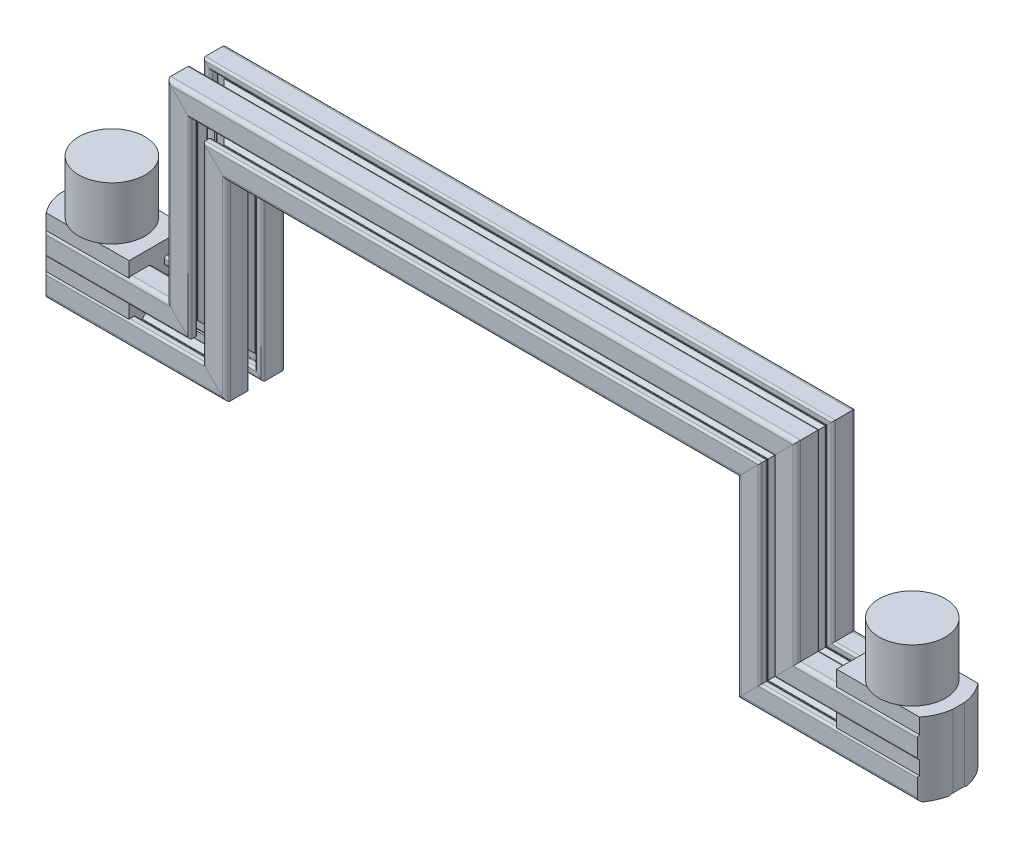
SolidWorks part; units mm, degrees
material "Commercially Pure CP-Ti UNS R50400 (SS)"
ref_plane "Front Plane" through (0, 0, 0) normal (0, 0, 1) x (1, 0, 0)
ref_plane "Top Plane" through (0, 0, 0) normal (0, 1, 0) x (1, 0, 0)
ref_plane "Right Plane" through (0, 0, 0) normal (1, 0, 0) x (0, 0, -1)
sketch "Sketch7" plane through (0, 0, 0) normal (1, 0, 0) x (0, 0, -1)
  line L0 (13.9698, 21.2743) -> (13.5298, 21.2743)
  line L1 (12.0298, 22.7743) -> (12.0298, 23.2743)
  line L2 (13.5298, 24.7743) -> (23.1398, 24.7743)
  line L3 (25.4198, 22.4943) -> (25.4198, 12.8843)
  line L4 (23.9198, 11.3843) -> (23.4198, 11.3843)
  line L5 (21.9198, 12.8843) -> (21.9198, 13.3243)
  line L6 (20.9198, 14.3243) -> (15.3498, 14.3243)
  line L7 (14.9698, 14.7043) -> (14.9698, 20.2743)
  line L8 (21.9589, -6.6897) -> (21.9589, -6.2497)
  line L9 (23.4589, -4.7497) -> (23.9589, -4.7497)
  line L10 (25.4589, -6.2497) -> (25.4589, -15.8597)
  line L11 (23.1789, -18.1397) -> (13.5689, -18.1397)
  line L12 (12.0689, -16.6397) -> (12.0689, -16.1397)
  line L13 (13.5689, -14.6397) -> (14.0089, -14.6397)
  line L14 (15.0089, -13.6397) -> (15.0089, -8.0697)
  line L15 (15.3889, -7.6897) -> (20.9589, -7.6897)
  line L16 (-6.0052, -14.6787) -> (-5.5652, -14.6787)
  line L17 (-4.0652, -16.1787) -> (-4.0652, -16.6787)
  line L18 (-5.5652, -18.1787) -> (-15.1752, -18.1787)
  line L19 (-17.4552, -15.8987) -> (-17.4552, -6.2887)
  line L20 (-15.9552, -4.7887) -> (-15.4552, -4.7887)
  line L21 (-13.9552, -6.2887) -> (-13.9552, -6.7287)
  line L22 (-12.9552, -7.7287) -> (-7.3852, -7.7287)
  line L23 (-7.0052, -8.1087) -> (-7.0052, -13.6787)
  line L24 (1.8289, -2.4886) -> (1.4132, -2.3164)
  line L25 (-1.632, 0.7289) -> (-1.8042, 1.1447)
  line L26 (-1.804, 5.4512) -> (-1.6318, 5.867)
  line L27 (1.4134, 8.9121) -> (1.8292, 9.0843)
  line L28 (6.1358, 9.0842) -> (6.5515, 8.912)
  line L29 (9.5966, 5.8667) -> (9.7688, 5.451)
  line L30 (9.7687, 1.1444) -> (9.5965, 0.7287)
  line L31 (6.5512, -2.3165) -> (6.1355, -2.4887)
  line L32 (-13.9942, 13.2853) -> (-13.9942, 12.8453)
  line L33 (-15.4942, 11.3453) -> (-15.9942, 11.3453)
  line L34 (-17.4942, 12.8453) -> (-17.4942, 22.4553)
  line L35 (-15.2142, 24.7353) -> (-5.6042, 24.7353)
  line L36 (-4.1042, 23.2353) -> (-4.1042, 22.7353)
  line L37 (-5.6042, 21.2353) -> (-6.0442, 21.2353)
  line L38 (-7.0442, 20.2353) -> (-7.0442, 14.6653)
  line L39 (-7.4242, 14.2853) -> (-12.9942, 14.2853)
  line L40 (4.9058, 11.2153) -> (4.0058, 10.7002)
  line L41 (4.0058, 10.7002) -> (3.1058, 11.2153)
  line L42 (3.1058, 11.2153) -> (-2.1975, 11.2153)
  line L43 (-2.4662, 11.3266) -> (-5.9329, 14.7933)
  line L44 (-6.0442, 15.062) -> (-6.0442, 19.3553)
  line L45 (-5.6642, 19.7353) -> (-2.5792, 19.7353)
  line L46 (-1.0592, 21.2553) -> (-1.0592, 24.2153)
  line L47 (-2.5792, 25.7353) -> (-15.4942, 25.7353)
  line L48 (-18.4942, 22.7353) -> (-18.4942, 9.8203)
  line L49 (-16.9742, 8.3003) -> (-14.0142, 8.3003)
  line L50 (-12.4942, 9.8203) -> (-12.4942, 12.9053)
  line L51 (-12.1142, 13.2853) -> (-7.8138, 13.2853)
  line L52 (-7.5451, 13.174) -> (-4.0855, 9.7144)
  line L53 (-3.9742, 9.4457) -> (-3.9742, 4.1353)
  line L54 (-3.9742, 4.1353) -> (-3.4546, 3.2353)
  line L55 (-3.4546, 3.2353) -> (-3.9742, 2.3353)
  line L56 (-3.9742, 2.3353) -> (-3.9742, -2.968)
  line L57 (-4.0855, -3.2367) -> (-7.5522, -6.7034)
  line L58 (-7.8209, -6.8147) -> (-12.1142, -6.8147)
  line L59 (-12.4942, -6.4347) -> (-12.4942, -3.3497)
  line L60 (-14.0142, -1.8297) -> (-16.9742, -1.8297)
  line L61 (-18.4942, -3.3497) -> (-18.4942, -16.2647)
  line L62 (-15.4942, -19.2647) -> (-2.5792, -19.2647)
  line L63 (-1.0592, -17.7447) -> (-1.0592, -14.7847)
  line L64 (-2.5792, -13.2647) -> (-5.6642, -13.2647)
  line L65 (-6.0442, -12.8847) -> (-6.0442, -8.5843)
  line L66 (-5.9329, -8.3156) -> (-2.4733, -4.856)
  line L67 (-2.2046, -4.7447) -> (3.1058, -4.7447)
  line L68 (3.1058, -4.7447) -> (4.0058, -4.2295)
  line L69 (4.0058, -4.2295) -> (4.9058, -4.7447)
  line L70 (4.9058, -4.7447) -> (10.2091, -4.7447)
  line L71 (10.4778, -4.856) -> (13.9445, -8.3227)
  line L72 (14.0558, -8.5914) -> (14.0558, -12.8847)
  line L73 (13.6758, -13.2647) -> (10.5908, -13.2647)
  line L74 (9.0708, -14.7847) -> (9.0708, -17.7447)
  line L75 (10.5908, -19.2647) -> (23.5058, -19.2647)
  line L76 (26.5058, -16.2647) -> (26.5058, -3.3497)
  line L77 (24.9858, -1.8297) -> (22.0258, -1.8297)
  line L78 (20.5058, -3.3497) -> (20.5058, -6.4347)
  line L79 (20.1258, -6.8147) -> (15.8254, -6.8147)
  line L80 (15.5567, -6.7034) -> (12.0971, -3.2438)
  line L81 (11.9858, -2.9751) -> (11.9858, 2.3353)
  line L82 (11.9858, 2.3353) -> (11.4662, 3.2353)
  line L83 (11.4662, 3.2353) -> (11.9858, 4.1353)
  line L84 (11.9858, 4.1353) -> (11.9858, 9.4386)
  line L85 (12.0971, 9.7073) -> (15.5638, 13.174)
  line L86 (15.8325, 13.2853) -> (20.1258, 13.2853)
  line L87 (20.5058, 12.9053) -> (20.5058, 9.8203)
  line L88 (22.0258, 8.3003) -> (24.9858, 8.3003)
  line L89 (26.5058, 9.8203) -> (26.5058, 22.7353)
  line L90 (23.5058, 25.7353) -> (10.5908, 25.7353)
  line L91 (9.0708, 24.2153) -> (9.0708, 21.2553)
  line L92 (10.5908, 19.7353) -> (13.6758, 19.7353)
  line L93 (14.0558, 19.3553) -> (14.0558, 15.0549)
  line L94 (13.9445, 14.7862) -> (10.4849, 11.3266)
  line L95 (10.2162, 11.2153) -> (4.9058, 11.2153)
  arc A0 (14.9698, 20.2743) -> (13.9698, 21.2743) centre (13.9698, 20.2743) ccw
  arc A1 (12.0298, 22.7743) -> (13.5298, 21.2743) centre (13.5298, 22.7743) ccw
  arc A2 (13.5298, 24.7743) -> (12.0298, 23.2743) centre (13.5298, 23.2743) ccw
  arc A3 (25.4198, 22.4943) -> (23.1398, 24.7743) centre (23.1398, 22.4943) ccw
  arc A4 (23.9198, 11.3843) -> (25.4198, 12.8843) centre (23.9198, 12.8843) ccw
  arc A5 (21.9198, 12.8843) -> (23.4198, 11.3843) centre (23.4198, 12.8843) ccw
  arc A6 (21.9198, 13.3243) -> (20.9198, 14.3243) centre (20.9198, 13.3243) ccw
  arc A7 (14.9698, 14.7043) -> (15.3498, 14.3243) centre (15.3498, 14.7043) ccw
  arc A8 (20.9589, -7.6897) -> (21.9589, -6.6897) centre (20.9589, -6.6897) ccw
  arc A9 (23.4589, -4.7497) -> (21.9589, -6.2497) centre (23.4589, -6.2497) ccw
  arc A10 (25.4589, -6.2497) -> (23.9589, -4.7497) centre (23.9589, -6.2497) ccw
  arc A11 (23.1789, -18.1397) -> (25.4589, -15.8597) centre (23.1789, -15.8597) ccw
  arc A12 (12.0689, -16.6397) -> (13.5689, -18.1397) centre (13.5689, -16.6397) ccw
  arc A13 (13.5689, -14.6397) -> (12.0689, -16.1397) centre (13.5689, -16.1397) ccw
  arc A14 (14.0089, -14.6397) -> (15.0089, -13.6397) centre (14.0089, -13.6397) ccw
  arc A15 (15.3889, -7.6897) -> (15.0089, -8.0697) centre (15.3889, -8.0697) ccw
  arc A16 (-7.0052, -13.6787) -> (-6.0052, -14.6787) centre (-6.0052, -13.6787) ccw
  arc A17 (-4.0652, -16.1787) -> (-5.5652, -14.6787) centre (-5.5652, -16.1787) ccw
  arc A18 (-5.5652, -18.1787) -> (-4.0652, -16.6787) centre (-5.5652, -16.6787) ccw
  arc A19 (-17.4552, -15.8987) -> (-15.1752, -18.1787) centre (-15.1752, -15.8987) ccw
  arc A20 (-15.9552, -4.7887) -> (-17.4552, -6.2887) centre (-15.9552, -6.2887) ccw
  arc A21 (-13.9552, -6.2887) -> (-15.4552, -4.7887) centre (-15.4552, -6.2887) ccw
  arc A22 (-13.9552, -6.7287) -> (-12.9552, -7.7287) centre (-12.9552, -6.7287) ccw
  arc A23 (-7.0052, -8.1087) -> (-7.3852, -7.7287) centre (-7.3852, -8.1087) ccw
  arc A24 (1.0363, -0.7421) -> (1.4132, -2.3164) centre (1.7959, -1.3925) ccw
  arc A25 (-0.0577, 0.352) -> (1.0363, -0.7421) centre (3.9823, 3.2978) ccw
  arc A26 (-1.632, 0.7289) -> (-0.0577, 0.352) centre (-0.7081, 1.1116) ccw
  arc A27 (-0.9575, 2.5244) -> (-1.8042, 1.1447) centre (-0.8803, 1.5274) ccw
  arc A28 (-0.9574, 4.0715) -> (-0.9575, 2.5244) centre (3.9823, 3.2978) ccw
  arc A29 (-1.804, 5.4512) -> (-0.9574, 4.0715) centre (-0.8802, 5.0686) ccw
  arc A30 (-0.0575, 6.2439) -> (-1.6318, 5.867) centre (-0.708, 5.4843) ccw
  arc A31 (1.0365, 7.3379) -> (-0.0575, 6.2439) centre (3.9823, 3.2978) ccw
  arc A32 (1.4134, 8.9121) -> (1.0365, 7.3379) centre (1.7961, 7.9882) ccw
  arc A33 (3.2089, 8.2376) -> (1.8292, 9.0843) centre (2.2119, 8.1604) ccw
  arc A34 (4.7561, 8.2376) -> (3.2089, 8.2376) centre (3.9823, 3.2978) ccw
  arc A35 (6.1358, 9.0842) -> (4.7561, 8.2376) centre (5.7531, 8.1603) ccw
  arc A36 (6.9284, 7.3377) -> (6.5515, 8.912) centre (6.1688, 7.9881) ccw
  arc A37 (8.0224, 6.2437) -> (6.9284, 7.3377) centre (3.9823, 3.2978) ccw
  arc A38 (9.5966, 5.8667) -> (8.0224, 6.2437) centre (8.6727, 5.484) ccw
  arc A39 (8.9222, 4.0713) -> (9.7688, 5.451) centre (8.845, 5.0683) ccw
  arc A40 (8.9221, 2.5241) -> (8.9222, 4.0713) centre (3.9823, 3.2978) ccw
  arc A41 (9.7687, 1.1444) -> (8.9221, 2.5241) centre (8.8448, 1.5271) ccw
  arc A42 (8.0222, 0.3518) -> (9.5965, 0.7287) centre (8.6726, 1.1113) ccw
  arc A43 (6.9282, -0.7422) -> (8.0222, 0.3518) centre (3.9823, 3.2978) ccw
  arc A44 (6.5512, -2.3165) -> (6.9282, -0.7422) centre (6.1685, -1.3926) ccw
  arc A45 (4.7558, -1.642) -> (6.1355, -2.4887) centre (5.7528, -1.5648) ccw
  arc A46 (3.2086, -1.642) -> (4.7558, -1.642) centre (3.9823, 3.2978) ccw
  arc A47 (1.8289, -2.4886) -> (3.2086, -1.642) centre (2.2116, -1.5647) ccw
  arc A48 (-12.9942, 14.2853) -> (-13.9942, 13.2853) centre (-12.9942, 13.2853) ccw
  arc A49 (-15.4942, 11.3453) -> (-13.9942, 12.8453) centre (-15.4942, 12.8453) ccw
  arc A50 (-17.4942, 12.8453) -> (-15.9942, 11.3453) centre (-15.9942, 12.8453) ccw
  arc A51 (-15.2142, 24.7353) -> (-17.4942, 22.4553) centre (-15.2142, 22.4553) ccw
  arc A52 (-4.1042, 23.2353) -> (-5.6042, 24.7353) centre (-5.6042, 23.2353) ccw
  arc A53 (-5.6042, 21.2353) -> (-4.1042, 22.7353) centre (-5.6042, 22.7353) ccw
  arc A54 (-6.0442, 21.2353) -> (-7.0442, 20.2353) centre (-6.0442, 20.2353) ccw
  arc A55 (-7.4242, 14.2853) -> (-7.0442, 14.6653) centre (-7.4242, 14.6653) ccw
  arc A56 (-2.4662, 11.3266) -> (-2.1975, 11.2153) centre (-2.1975, 11.5953) ccw
  arc A57 (-6.0442, 15.062) -> (-5.9329, 14.7933) centre (-5.6642, 15.062) ccw
  arc A58 (-5.6642, 19.7353) -> (-6.0442, 19.3553) centre (-5.6642, 19.3553) ccw
  arc A59 (-2.5792, 19.7353) -> (-1.0592, 21.2553) centre (-2.5792, 21.2553) ccw
  arc A60 (-1.0592, 24.2153) -> (-2.5792, 25.7353) centre (-2.5792, 24.2153) ccw
  arc A61 (-15.4942, 25.7353) -> (-18.4942, 22.7353) centre (-15.4942, 22.7353) ccw
  arc A62 (-18.4942, 9.8203) -> (-16.9742, 8.3003) centre (-16.9742, 9.8203) ccw
  arc A63 (-14.0142, 8.3003) -> (-12.4942, 9.8203) centre (-14.0142, 9.8203) ccw
  arc A64 (-12.1142, 13.2853) -> (-12.4942, 12.9053) centre (-12.1142, 12.9053) ccw
  arc A65 (-7.5451, 13.174) -> (-7.8138, 13.2853) centre (-7.8138, 12.9053) ccw
  arc A66 (-3.9742, 9.4457) -> (-4.0855, 9.7144) centre (-4.3542, 9.4457) ccw
  arc A67 (-4.0855, -3.2367) -> (-3.9742, -2.968) centre (-4.3542, -2.968) ccw
  arc A68 (-7.8209, -6.8147) -> (-7.5522, -6.7034) centre (-7.8209, -6.4347) ccw
  arc A69 (-12.4942, -6.4347) -> (-12.1142, -6.8147) centre (-12.1142, -6.4347) ccw
  arc A70 (-12.4942, -3.3497) -> (-14.0142, -1.8297) centre (-14.0142, -3.3497) ccw
  arc A71 (-16.9742, -1.8297) -> (-18.4942, -3.3497) centre (-16.9742, -3.3497) ccw
  arc A72 (-18.4942, -16.2647) -> (-15.4942, -19.2647) centre (-15.4942, -16.2647) ccw
  arc A73 (-2.5792, -19.2647) -> (-1.0592, -17.7447) centre (-2.5792, -17.7447) ccw
  arc A74 (-1.0592, -14.7847) -> (-2.5792, -13.2647) centre (-2.5792, -14.7847) ccw
  arc A75 (-6.0442, -12.8847) -> (-5.6642, -13.2647) centre (-5.6642, -12.8847) ccw
  arc A76 (-5.9329, -8.3156) -> (-6.0442, -8.5843) centre (-5.6642, -8.5843) ccw
  arc A77 (-2.2046, -4.7447) -> (-2.4733, -4.856) centre (-2.2046, -5.1247) ccw
  arc A78 (10.4778, -4.856) -> (10.2091, -4.7447) centre (10.2091, -5.1247) ccw
  arc A79 (14.0558, -8.5914) -> (13.9445, -8.3227) centre (13.6758, -8.5914) ccw
  arc A80 (13.6758, -13.2647) -> (14.0558, -12.8847) centre (13.6758, -12.8847) ccw
  arc A81 (10.5908, -13.2647) -> (9.0708, -14.7847) centre (10.5908, -14.7847) ccw
  arc A82 (9.0708, -17.7447) -> (10.5908, -19.2647) centre (10.5908, -17.7447) ccw
  arc A83 (23.5058, -19.2647) -> (26.5058, -16.2647) centre (23.5058, -16.2647) ccw
  arc A84 (26.5058, -3.3497) -> (24.9858, -1.8297) centre (24.9858, -3.3497) ccw
  arc A85 (22.0258, -1.8297) -> (20.5058, -3.3497) centre (22.0258, -3.3497) ccw
  arc A86 (20.1258, -6.8147) -> (20.5058, -6.4347) centre (20.1258, -6.4347) ccw
  arc A87 (15.5567, -6.7034) -> (15.8254, -6.8147) centre (15.8254, -6.4347) ccw
  arc A88 (11.9858, -2.9751) -> (12.0971, -3.2438) centre (12.3658, -2.9751) ccw
  arc A89 (12.0971, 9.7073) -> (11.9858, 9.4386) centre (12.3658, 9.4386) ccw
  arc A90 (15.8325, 13.2853) -> (15.5638, 13.174) centre (15.8325, 12.9053) ccw
  arc A91 (20.5058, 12.9053) -> (20.1258, 13.2853) centre (20.1258, 12.9053) ccw
  arc A92 (20.5058, 9.8203) -> (22.0258, 8.3003) centre (22.0258, 9.8203) ccw
  arc A93 (24.9858, 8.3003) -> (26.5058, 9.8203) centre (24.9858, 9.8203) ccw
  arc A94 (26.5058, 22.7353) -> (23.5058, 25.7353) centre (23.5058, 22.7353) ccw
  arc A95 (10.5908, 25.7353) -> (9.0708, 24.2153) centre (10.5908, 24.2153) ccw
  arc A96 (9.0708, 21.2553) -> (10.5908, 19.7353) centre (10.5908, 21.2553) ccw
  arc A97 (14.0558, 19.3553) -> (13.6758, 19.7353) centre (13.6758, 19.3553) ccw
  arc A98 (13.9445, 14.7862) -> (14.0558, 15.0549) centre (13.6758, 15.0549) ccw
  arc A99 (10.2162, 11.2153) -> (10.4849, 11.3266) centre (10.2162, 11.5953) ccw
sketch "Sketch1" plane through (0, 0, 0) normal (0, 0, 1) x (1, 0, 0)
  line L0 (0, 0) -> (125, 0)
  line L1 (125, 0) -> (125, 144.6943)
  line L2 (125, 144.6943) -> (337, 144.6943)
  dimension "D1" = 337
  dimension "D2" = 125
sketch "Sketch2" [suppressed] plane through (0, 0, 0) normal (1, 0, 0) x (0, 0, -1)
  line L0 (-33.5, -41) -> (-31.5, -41)
  line L1 (-31.5, -43) -> (-42, -43)
  line L2 (-43, -42) -> (-43, -31.5)
  line L3 (-41, -31.5) -> (-41, -33.5)
  line L4 (-40, -34.5) -> (-34.88, -34.5)
  line L5 (-34.5, -34.88) -> (-34.5, -40)
  line L6 (-16.657, -26.2238) -> (-18.284, -25.188)
  line L7 (-19.8123, -26.7162) -> (-18.7764, -28.3429)
  line L8 (-21.0015, -29.2647) -> (-21.4195, -27.3819)
  line L9 (-23.5808, -27.3818) -> (-23.9986, -29.2645)
  line L10 (-26.2238, -28.343) -> (-25.188, -26.716)
  line L11 (-26.7162, -25.1877) -> (-28.3429, -26.2236)
  line L12 (-29.2647, -23.9985) -> (-27.3819, -23.5805)
  line L13 (-27.3818, -21.4192) -> (-29.2645, -21.0014)
  line L14 (-28.343, -18.7762) -> (-26.716, -19.812)
  line L15 (-25.1877, -18.2838) -> (-26.2236, -16.6571)
  line L16 (-23.9985, -15.7353) -> (-23.5805, -17.6181)
  line L17 (-21.4192, -17.6182) -> (-21.0014, -15.7355)
  line L18 (-18.7762, -16.657) -> (-19.812, -18.284)
  line L19 (-18.2838, -19.8123) -> (-16.6571, -18.7764)
  line L20 (-15.7353, -21.0015) -> (-17.6181, -21.4195)
  line L21 (-17.6182, -23.5808) -> (-15.7355, -23.9986)
  line L22 (41, -33.5) -> (41, -31.5)
  line L23 (43, -31.5) -> (43, -42)
  line L24 (42, -43) -> (31.5, -43)
  line L25 (31.5, -41) -> (33.5, -41)
  line L26 (34.5, -40) -> (34.5, -34.88)
  line L27 (34.88, -34.5) -> (40, -34.5)
  line L28 (26.7162, -19.8123) -> (28.3429, -18.7764)
  line L29 (29.2647, -21.0015) -> (27.3819, -21.4195)
  line L30 (27.3818, -23.5808) -> (29.2645, -23.9986)
  line L31 (28.343, -26.2238) -> (26.716, -25.188)
  line L32 (25.1877, -26.7162) -> (26.2236, -28.3429)
  line L33 (23.9985, -29.2647) -> (23.5805, -27.3819)
  line L34 (21.4192, -27.3818) -> (21.0014, -29.2645)
  line L35 (18.7762, -28.343) -> (19.812, -26.716)
  line L36 (18.2838, -25.1877) -> (16.6571, -26.2236)
  line L37 (15.7353, -23.9985) -> (17.6181, -23.5805)
  line L38 (17.6182, -21.4192) -> (15.7355, -21.0014)
  line L39 (16.657, -18.7762) -> (18.284, -19.812)
  line L40 (19.8123, -18.2838) -> (18.7764, -16.6571)
  line L41 (21.0015, -15.7353) -> (21.4195, -17.6181)
  line L42 (23.5808, -17.6182) -> (23.9986, -15.7355)
  line L43 (26.2238, -16.657) -> (25.188, -18.284)
  line L44 (34.5, 34.88) -> (34.5, 40)
  line L45 (33.5, 41) -> (31.5, 41)
  line L46 (31.5, 43) -> (42, 43)
  line L47 (43, 42) -> (43, 31.5)
  line L48 (41, 31.5) -> (41, 33.5)
  line L49 (40, 34.5) -> (34.88, 34.5)
  line L50 (26.7162, 25.1877) -> (28.3429, 26.2236)
  line L51 (29.2647, 23.9985) -> (27.3819, 23.5805)
  line L52 (27.3818, 21.4192) -> (29.2645, 21.0014)
  line L53 (28.343, 18.7762) -> (26.716, 19.812)
  line L54 (25.1877, 18.2838) -> (26.2236, 16.6571)
  line L55 (23.9985, 15.7353) -> (23.5805, 17.6181)
  line L56 (21.4192, 17.6182) -> (21.0014, 15.7355)
  line L57 (18.7762, 16.657) -> (19.812, 18.284)
  line L58 (18.2838, 19.8123) -> (16.6571, 18.7764)
  line L59 (15.7353, 21.0015) -> (17.6181, 21.4195)
  line L60 (17.6182, 23.5808) -> (15.7355, 23.9986)
  line L61 (16.657, 26.2238) -> (18.284, 25.188)
  line L62 (19.8123, 26.7162) -> (18.7764, 28.3429)
  line L63 (21.0015, 29.2647) -> (21.4195, 27.3819)
  line L64 (23.5808, 27.3818) -> (23.9986, 29.2645)
  line L65 (26.2238, 28.343) -> (25.188, 26.716)
  line L66 (-41, 33.5) -> (-41, 31.5)
  line L67 (-43, 31.5) -> (-43, 42)
  line L68 (-42, 43) -> (-31.5, 43)
  line L69 (-31.5, 41) -> (-33.5, 41)
  line L70 (-34.5, 40) -> (-34.5, 34.88)
  line L71 (-34.88, 34.5) -> (-40, 34.5)
  line L72 (-16.657, 18.7762) -> (-18.284, 19.812)
  line L73 (-19.8123, 18.2838) -> (-18.7764, 16.6571)
  line L74 (-21.0015, 15.7353) -> (-21.4195, 17.6181)
  line L75 (-23.5808, 17.6182) -> (-23.9986, 15.7355)
  line L76 (-26.2238, 16.657) -> (-25.188, 18.284)
  line L77 (-26.7162, 19.8123) -> (-28.3429, 18.7764)
  line L78 (-29.2647, 21.0015) -> (-27.3819, 21.4195)
  line L79 (-27.3818, 23.5808) -> (-29.2645, 23.9986)
  line L80 (-28.343, 26.2238) -> (-26.716, 25.188)
  line L81 (-25.1877, 26.7162) -> (-26.2236, 28.3429)
  line L82 (-23.9985, 29.2647) -> (-23.5805, 27.3819)
  line L83 (-21.4192, 27.3818) -> (-21.0014, 29.2645)
  line L84 (-18.7762, 28.343) -> (-19.812, 26.716)
  line L85 (-18.2838, 25.1877) -> (-16.6571, 26.2236)
  line L86 (-15.7353, 23.9985) -> (-17.6181, 23.5805)
  line L87 (-17.6182, 21.4192) -> (-15.7355, 21.0014)
  line L88 (39, -10.16) -> (33.3774, -10.16)
  line L89 (31.9632, -10.7458) -> (29.8203, -12.8887)
  line L90 (29.5516, -13) -> (23.4, -13)
  line L91 (23.4, -13) -> (22.5, -13.5151)
  line L92 (22.5, -13.5151) -> (21.6, -13)
  line L93 (21.6, -13) -> (15, -13)
  line L94 (13, -15) -> (13, -21.6)
  line L95 (13, -21.6) -> (13.5196, -22.5)
  line L96 (13.5196, -22.5) -> (13, -23.4)
  line L97 (13, -23.4) -> (13, -29.5516)
  line L98 (12.8887, -29.8203) -> (11.3787, -31.3303)
  line L99 (10.5, -33.4516) -> (10.5, -40)
  line L100 (11.5, -41) -> (13.5, -41)
  line L101 (13.5, -43) -> (-13.5, -43)
  line L102 (-13.5, -41) -> (-11.5, -41)
  line L103 (-10.5, -40) -> (-10.5, -33.4516)
  line L104 (-11.3787, -31.3303) -> (-12.8887, -29.8203)
  line L105 (-13, -29.5516) -> (-13, -23.4)
  line L106 (-13, -23.4) -> (-13.5196, -22.5)
  line L107 (-13.5196, -22.5) -> (-13, -21.6)
  line L108 (-13, -21.6) -> (-13, -15)
  line L109 (-15, -13) -> (-21.6, -13)
  line L110 (-21.6, -13) -> (-22.5, -13.5151)
  line L111 (-22.5, -13.5151) -> (-23.4, -13)
  line L112 (-23.4, -13) -> (-29.5516, -13)
  line L113 (-29.8203, -12.8887) -> (-31.9632, -10.7458)
  line L114 (-33.3774, -10.16) -> (-39, -10.16)
  line L115 (-41, -12.16) -> (-41, -13.5)
  line L116 (-43, -13.5) -> (-43, 13.5)
  line L117 (-41, 13.5) -> (-41, 12.16)
  line L118 (-39, 10.16) -> (-33.3774, 10.16)
  line L119 (-31.9632, 10.7458) -> (-29.8203, 12.8887)
  line L120 (-29.5516, 13) -> (-23.4, 13)
  line L121 (-23.4, 13) -> (-22.5, 13.5151)
  line L122 (-22.5, 13.5151) -> (-21.6, 13)
  line L123 (-21.6, 13) -> (-15, 13)
  line L124 (-13, 15) -> (-13, 21.6)
  line L125 (-13, 21.6) -> (-13.5196, 22.5)
  line L126 (-13.5196, 22.5) -> (-13, 23.4)
  line L127 (-13, 23.4) -> (-13, 29.5516)
  line L128 (-12.8887, 29.8203) -> (-11.3787, 31.3303)
  line L129 (-10.5, 33.4516) -> (-10.5, 40)
  line L130 (-11.5, 41) -> (-13.5, 41)
  line L131 (-13.5, 43) -> (13.5, 43)
  line L132 (13.5, 41) -> (11.5, 41)
  line L133 (10.5, 40) -> (10.5, 33.4516)
  line L134 (11.3787, 31.3303) -> (12.8887, 29.8203)
  line L135 (13, 29.5516) -> (13, 23.4)
  line L136 (13, 23.4) -> (13.5196, 22.5)
  line L137 (13.5196, 22.5) -> (13, 21.6)
  line L138 (13, 21.6) -> (13, 15)
  line L139 (15, 13) -> (21.6, 13)
  line L140 (21.6, 13) -> (22.5, 13.5151)
  line L141 (22.5, 13.5151) -> (23.4, 13)
  line L142 (23.4, 13) -> (29.5516, 13)
  line L143 (29.8203, 12.8887) -> (31.9581, 10.7509)
  line L144 (33.3723, 10.1651) -> (39, 10.1651)
  line L145 (41, 12.1651) -> (41, 13.5)
  line L146 (43, 13.5) -> (43, -13.5)
  line L147 (41, -13.5) -> (41, -12.16)
  line L148 (45, -15.915) -> (45, 15.915)
  line L149 (43.48, 17.435) -> (40.52, 17.435)
  line L150 (39, 15.915) -> (39, 13.45)
  line L151 (38, 12.45) -> (34.9984, 12.45)
  line L152 (34.7297, 12.5613) -> (32.1113, 15.1797)
  line L153 (32, 15.4484) -> (32, 21.6)
  line L154 (32, 21.6) -> (31.4804, 22.5)
  line L155 (31.4804, 22.5) -> (32, 23.4)
  line L156 (32, 23.4) -> (32, 29.5516)
  line L157 (32.1113, 29.8203) -> (34.7297, 32.4387)
  line L158 (34.9984, 32.55) -> (38, 32.55)
  line L159 (39, 31.55) -> (39, 29.085)
  line L160 (40.52, 27.565) -> (43.48, 27.565)
  line L161 (45, 29.085) -> (45, 42)
  line L162 (42, 45) -> (29.085, 45)
  line L163 (27.565, 43.48) -> (27.565, 40.52)
  line L164 (29.085, 39) -> (31.55, 39)
  line L165 (32.55, 38) -> (32.55, 34.9984)
  line L166 (32.4387, 34.7297) -> (29.8203, 32.1113)
  line L167 (29.5516, 32) -> (23.4, 32)
  line L168 (23.4, 32) -> (22.5, 31.4849)
  line L169 (22.5, 31.4849) -> (21.6, 32)
  line L170 (21.6, 32) -> (15.4484, 32)
  line L171 (15.1797, 32.1113) -> (12.5613, 34.7297)
  line L172 (12.45, 34.9984) -> (12.45, 38)
  line L173 (13.45, 39) -> (15.915, 39)
  line L174 (17.435, 40.52) -> (17.435, 43.48)
  line L175 (15.915, 45) -> (-15.915, 45)
  line L176 (-17.435, 43.48) -> (-17.435, 40.52)
  line L177 (-15.915, 39) -> (-13.45, 39)
  line L178 (-12.45, 38) -> (-12.45, 34.9984)
  line L179 (-12.5613, 34.7297) -> (-15.1797, 32.1113)
  line L180 (-15.4484, 32) -> (-21.6, 32)
  line L181 (-21.6, 32) -> (-22.5, 31.4849)
  line L182 (-22.5, 31.4849) -> (-23.4, 32)
  line L183 (-23.4, 32) -> (-29.5516, 32)
  line L184 (-29.8203, 32.1113) -> (-32.4387, 34.7297)
  line L185 (-32.55, 34.9984) -> (-32.55, 38)
  line L186 (-31.55, 39) -> (-29.085, 39)
  line L187 (-27.565, 40.52) -> (-27.565, 43.48)
  line L188 (-29.085, 45) -> (-42, 45)
  line L189 (-45, 42) -> (-45, 29.085)
  line L190 (-43.48, 27.565) -> (-40.52, 27.565)
  line L191 (-39, 29.085) -> (-39, 31.55)
  line L192 (-38, 32.55) -> (-34.9984, 32.55)
  line L193 (-34.7297, 32.4387) -> (-32.1113, 29.8203)
  line L194 (-32, 29.5516) -> (-32, 23.4)
  line L195 (-32, 23.4) -> (-31.4804, 22.5)
  line L196 (-31.4804, 22.5) -> (-32, 21.6)
  line L197 (-32, 21.6) -> (-32, 15.4484)
  line L198 (-32.1113, 15.1797) -> (-34.7297, 12.5613)
  line L199 (-34.9984, 12.45) -> (-38, 12.45)
  line L200 (-39, 13.45) -> (-39, 15.915)
  line L201 (-40.52, 17.435) -> (-43.48, 17.435)
  line L202 (-45, 15.915) -> (-45, -15.915)
  line L203 (-43.48, -17.435) -> (-40.52, -17.435)
  line L204 (-39, -15.915) -> (-39, -13.45)
  line L205 (-38, -12.45) -> (-34.9984, -12.45)
  line L206 (-34.7297, -12.5613) -> (-32.1113, -15.1797)
  line L207 (-32, -15.4484) -> (-32, -21.6)
  line L208 (-32, -21.6) -> (-31.4804, -22.5)
  line L209 (-31.4804, -22.5) -> (-32, -23.4)
  line L210 (-32, -23.4) -> (-32, -29.5516)
  line L211 (-32.1113, -29.8203) -> (-34.7297, -32.4387)
  line L212 (-34.9984, -32.55) -> (-38, -32.55)
  line L213 (-39, -31.55) -> (-39, -29.085)
  line L214 (-40.52, -27.565) -> (-43.48, -27.565)
  line L215 (-45, -29.085) -> (-45, -42)
  line L216 (-42, -45) -> (-29.085, -45)
  line L217 (-27.565, -43.48) -> (-27.565, -40.52)
  line L218 (-29.085, -39) -> (-31.55, -39)
  line L219 (-32.55, -38) -> (-32.55, -34.9984)
  line L220 (-32.4387, -34.7297) -> (-29.8203, -32.1113)
  line L221 (-29.5516, -32) -> (-23.4, -32)
  line L222 (-23.4, -32) -> (-22.5, -31.4849)
  line L223 (-22.5, -31.4849) -> (-21.6, -32)
  line L224 (-21.6, -32) -> (-15.4484, -32)
  line L225 (-15.1797, -32.1113) -> (-12.5613, -34.7297)
  line L226 (-12.45, -34.9984) -> (-12.45, -38)
  line L227 (-13.45, -39) -> (-15.915, -39)
  line L228 (-17.435, -40.52) -> (-17.435, -43.48)
  line L229 (-15.915, -45) -> (15.915, -45)
  line L230 (17.435, -43.48) -> (17.435, -40.52)
  line L231 (15.915, -39) -> (13.45, -39)
  line L232 (12.45, -38) -> (12.45, -34.9984)
  line L233 (12.5613, -34.7297) -> (15.1797, -32.1113)
  line L234 (15.4484, -32) -> (21.6, -32)
  line L235 (21.6, -32) -> (22.5, -31.4849)
  line L236 (22.5, -31.4849) -> (23.4, -32)
  line L237 (23.4, -32) -> (29.5516, -32)
  line L238 (29.8203, -32.1113) -> (32.4387, -34.7297)
  line L239 (32.55, -34.9984) -> (32.55, -38)
  line L240 (31.55, -39) -> (29.085, -39)
  line L241 (27.565, -40.52) -> (27.565, -43.48)
  line L242 (29.085, -45) -> (42, -45)
  line L243 (45, -42) -> (45, -29.085)
  line L244 (43.48, -27.565) -> (40.52, -27.565)
  line L245 (39, -29.085) -> (39, -31.55)
  line L246 (38, -32.55) -> (34.9984, -32.55)
  line L247 (34.7297, -32.4387) -> (32.1113, -29.8203)
  line L248 (32, -29.5516) -> (32, -23.4)
  line L249 (32, -23.4) -> (31.4804, -22.5)
  line L250 (31.4804, -22.5) -> (32, -21.6)
  line L251 (32, -21.6) -> (32, -15.4484)
  line L252 (32.1113, -15.1797) -> (34.7297, -12.5613)
  line L253 (34.9984, -12.45) -> (38, -12.45)
  line L254 (39, -13.45) -> (39, -15.915)
  line L255 (40.52, -17.435) -> (43.48, -17.435)
  arc A0 (-34.5, -40) -> (-33.5, -41) centre (-33.5, -40) ccw
  arc A1 (-31.5, -43) -> (-31.5, -41) centre (-31.5, -42) ccw
  arc A2 (-43, -42) -> (-42, -43) centre (-42, -42) ccw
  arc A3 (-41, -31.5) -> (-43, -31.5) centre (-42, -31.5) ccw
  arc A4 (-41, -33.5) -> (-40, -34.5) centre (-40, -33.5) ccw
  arc A5 (-34.5, -34.88) -> (-34.88, -34.5) centre (-34.88, -34.88) ccw
  arc A6 (-15.2086, -25.7917) -> (-15.0167, -25.3284) centre (-22.5, -22.5) ccw
  arc A7 (-16.657, -26.2238) -> (-15.2086, -25.7917) centre (-16.12, -25.3802) ccw
  arc A8 (-19.8123, -26.7162) -> (-18.284, -25.188) centre (-22.5, -22.5) ccw
  arc A9 (-19.2085, -29.7915) -> (-18.7764, -28.3429) centre (-19.6199, -28.8801) ccw
  arc A10 (-19.6717, -29.9834) -> (-19.2085, -29.7915) centre (-22.5, -22.5) ccw
  arc A11 (-21.0015, -29.2647) -> (-19.6717, -29.9834) centre (-20.0253, -29.048) ccw
  arc A12 (-23.5808, -27.3818) -> (-21.4195, -27.3819) centre (-22.5, -22.5) ccw
  arc A13 (-25.3284, -29.9833) -> (-23.9986, -29.2645) centre (-24.9749, -29.0479) ccw
  arc A14 (-25.7917, -29.7914) -> (-25.3284, -29.9833) centre (-22.5, -22.5) ccw
  arc A15 (-26.2238, -28.343) -> (-25.7917, -29.7914) centre (-25.3802, -28.88) ccw
  arc A16 (-26.7162, -25.1877) -> (-25.188, -26.716) centre (-22.5, -22.5) ccw
  arc A17 (-29.7915, -25.7915) -> (-28.3429, -26.2236) centre (-28.8801, -25.3801) ccw
  arc A18 (-29.9834, -25.3283) -> (-29.7915, -25.7915) centre (-22.5, -22.5) ccw
  arc A19 (-29.2647, -23.9985) -> (-29.9834, -25.3283) centre (-29.048, -24.9747) ccw
  arc A20 (-27.3818, -21.4192) -> (-27.3819, -23.5805) centre (-22.5, -22.5) ccw
  arc A21 (-29.9833, -19.6716) -> (-29.2645, -21.0014) centre (-29.0479, -20.0251) ccw
  arc A22 (-29.7914, -19.2083) -> (-29.9833, -19.6716) centre (-22.5, -22.5) ccw
  arc A23 (-28.343, -18.7762) -> (-29.7914, -19.2083) centre (-28.88, -19.6198) ccw
  arc A24 (-25.1877, -18.2838) -> (-26.716, -19.812) centre (-22.5, -22.5) ccw
  arc A25 (-25.7915, -15.2085) -> (-26.2236, -16.6571) centre (-25.3801, -16.1199) ccw
  arc A26 (-25.3283, -15.0166) -> (-25.7915, -15.2085) centre (-22.5, -22.5) ccw
  arc A27 (-23.9985, -15.7353) -> (-25.3283, -15.0166) centre (-24.9747, -15.952) ccw
  arc A28 (-21.4192, -17.6182) -> (-23.5805, -17.6181) centre (-22.5, -22.5) ccw
  arc A29 (-19.6716, -15.0167) -> (-21.0014, -15.7355) centre (-20.0251, -15.9521) ccw
  arc A30 (-19.2083, -15.2086) -> (-19.6716, -15.0167) centre (-22.5, -22.5) ccw
  arc A31 (-18.7762, -16.657) -> (-19.2083, -15.2086) centre (-19.6198, -16.12) ccw
  arc A32 (-18.2838, -19.8123) -> (-19.812, -18.284) centre (-22.5, -22.5) ccw
  arc A33 (-15.2085, -19.2085) -> (-16.6571, -18.7764) centre (-16.1199, -19.6199) ccw
  arc A34 (-15.0166, -19.6717) -> (-15.2085, -19.2085) centre (-22.5, -22.5) ccw
  arc A35 (-15.7353, -21.0015) -> (-15.0166, -19.6717) centre (-15.952, -20.0253) ccw
  arc A36 (-17.6182, -23.5808) -> (-17.6181, -21.4195) centre (-22.5, -22.5) ccw
  arc A37 (-15.0167, -25.3284) -> (-15.7355, -23.9986) centre (-15.9521, -24.9749) ccw
  arc A38 (40, -34.5) -> (41, -33.5) centre (40, -33.5) ccw
  arc A39 (43, -31.5) -> (41, -31.5) centre (42, -31.5) ccw
  arc A40 (42, -43) -> (43, -42) centre (42, -42) ccw
  arc A41 (31.5, -41) -> (31.5, -43) centre (31.5, -42) ccw
  arc A42 (33.5, -41) -> (34.5, -40) centre (33.5, -40) ccw
  arc A43 (34.88, -34.5) -> (34.5, -34.88) centre (34.88, -34.88) ccw
  arc A44 (26.7162, -19.8123) -> (25.188, -18.284) centre (22.5, -22.5) ccw
  arc A45 (29.7915, -19.2085) -> (28.3429, -18.7764) centre (28.8801, -19.6199) ccw
  arc A46 (29.9834, -19.6717) -> (29.7915, -19.2085) centre (22.5, -22.5) ccw
  arc A47 (29.2647, -21.0015) -> (29.9834, -19.6717) centre (29.048, -20.0253) ccw
  arc A48 (27.3818, -23.5808) -> (27.3819, -21.4195) centre (22.5, -22.5) ccw
  arc A49 (29.9833, -25.3284) -> (29.2645, -23.9986) centre (29.0479, -24.9749) ccw
  arc A50 (29.7914, -25.7917) -> (29.9833, -25.3284) centre (22.5, -22.5) ccw
  arc A51 (28.343, -26.2238) -> (29.7914, -25.7917) centre (28.88, -25.3802) ccw
  arc A52 (25.1877, -26.7162) -> (26.716, -25.188) centre (22.5, -22.5) ccw
  arc A53 (25.7915, -29.7915) -> (26.2236, -28.3429) centre (25.3801, -28.8801) ccw
  arc A54 (25.3283, -29.9834) -> (25.7915, -29.7915) centre (22.5, -22.5) ccw
  arc A55 (23.9985, -29.2647) -> (25.3283, -29.9834) centre (24.9747, -29.048) ccw
  arc A56 (21.4192, -27.3818) -> (23.5805, -27.3819) centre (22.5, -22.5) ccw
  arc A57 (19.6716, -29.9833) -> (21.0014, -29.2645) centre (20.0251, -29.0479) ccw
  arc A58 (19.2083, -29.7914) -> (19.6716, -29.9833) centre (22.5, -22.5) ccw
  arc A59 (18.7762, -28.343) -> (19.2083, -29.7914) centre (19.6198, -28.88) ccw
  arc A60 (18.2838, -25.1877) -> (19.812, -26.716) centre (22.5, -22.5) ccw
  arc A61 (15.2085, -25.7915) -> (16.6571, -26.2236) centre (16.1199, -25.3801) ccw
  arc A62 (15.0166, -25.3283) -> (15.2085, -25.7915) centre (22.5, -22.5) ccw
  arc A63 (15.7353, -23.9985) -> (15.0166, -25.3283) centre (15.952, -24.9747) ccw
  arc A64 (17.6182, -21.4192) -> (17.6181, -23.5805) centre (22.5, -22.5) ccw
  arc A65 (15.0167, -19.6716) -> (15.7355, -21.0014) centre (15.9521, -20.0251) ccw
  arc A66 (15.2086, -19.2083) -> (15.0167, -19.6716) centre (22.5, -22.5) ccw
  arc A67 (16.657, -18.7762) -> (15.2086, -19.2083) centre (16.12, -19.6198) ccw
  arc A68 (19.8123, -18.2838) -> (18.284, -19.812) centre (22.5, -22.5) ccw
  arc A69 (19.2085, -15.2085) -> (18.7764, -16.6571) centre (19.6199, -16.1199) ccw
  arc A70 (19.6717, -15.0166) -> (19.2085, -15.2085) centre (22.5, -22.5) ccw
  arc A71 (21.0015, -15.7353) -> (19.6717, -15.0166) centre (20.0253, -15.952) ccw
  arc A72 (23.5808, -17.6182) -> (21.4195, -17.6181) centre (22.5, -22.5) ccw
  arc A73 (25.3284, -15.0167) -> (23.9986, -15.7355) centre (24.9749, -15.9521) ccw
  arc A74 (25.7917, -15.2086) -> (25.3284, -15.0167) centre (22.5, -22.5) ccw
  arc A75 (26.2238, -16.657) -> (25.7917, -15.2086) centre (25.3802, -16.12) ccw
  arc A76 (34.5, 34.88) -> (34.88, 34.5) centre (34.88, 34.88) ccw
  arc A77 (34.5, 40) -> (33.5, 41) centre (33.5, 40) ccw
  arc A78 (31.5, 43) -> (31.5, 41) centre (31.5, 42) ccw
  arc A79 (43, 42) -> (42, 43) centre (42, 42) ccw
  arc A80 (41, 31.5) -> (43, 31.5) centre (42, 31.5) ccw
  arc A81 (41, 33.5) -> (40, 34.5) centre (40, 33.5) ccw
  arc A82 (26.7162, 25.1877) -> (25.188, 26.716) centre (22.5, 22.5) ccw
  arc A83 (29.7915, 25.7915) -> (28.3429, 26.2236) centre (28.8801, 25.3801) ccw
  arc A84 (29.9834, 25.3283) -> (29.7915, 25.7915) centre (22.5, 22.5) ccw
  arc A85 (29.2647, 23.9985) -> (29.9834, 25.3283) centre (29.048, 24.9747) ccw
  arc A86 (27.3818, 21.4192) -> (27.3819, 23.5805) centre (22.5, 22.5) ccw
  arc A87 (29.9833, 19.6716) -> (29.2645, 21.0014) centre (29.0479, 20.0251) ccw
  arc A88 (29.7914, 19.2083) -> (29.9833, 19.6716) centre (22.5, 22.5) ccw
  arc A89 (28.343, 18.7762) -> (29.7914, 19.2083) centre (28.88, 19.6198) ccw
  arc A90 (25.1877, 18.2838) -> (26.716, 19.812) centre (22.5, 22.5) ccw
  arc A91 (25.7915, 15.2085) -> (26.2236, 16.6571) centre (25.3801, 16.1199) ccw
  arc A92 (25.3283, 15.0166) -> (25.7915, 15.2085) centre (22.5, 22.5) ccw
  arc A93 (23.9985, 15.7353) -> (25.3283, 15.0166) centre (24.9747, 15.952) ccw
  arc A94 (21.4192, 17.6182) -> (23.5805, 17.6181) centre (22.5, 22.5) ccw
  arc A95 (19.6716, 15.0167) -> (21.0014, 15.7355) centre (20.0251, 15.9521) ccw
  arc A96 (19.2083, 15.2086) -> (19.6716, 15.0167) centre (22.5, 22.5) ccw
  arc A97 (18.7762, 16.657) -> (19.2083, 15.2086) centre (19.6198, 16.12) ccw
  arc A98 (18.2838, 19.8123) -> (19.812, 18.284) centre (22.5, 22.5) ccw
  arc A99 (15.2085, 19.2085) -> (16.6571, 18.7764) centre (16.1199, 19.6199) ccw
  arc A100 (15.0166, 19.6717) -> (15.2085, 19.2085) centre (22.5, 22.5) ccw
  arc A101 (15.7353, 21.0015) -> (15.0166, 19.6717) centre (15.952, 20.0253) ccw
  arc A102 (17.6182, 23.5808) -> (17.6181, 21.4195) centre (22.5, 22.5) ccw
  arc A103 (15.0167, 25.3284) -> (15.7355, 23.9986) centre (15.9521, 24.9749) ccw
  arc A104 (15.2086, 25.7917) -> (15.0167, 25.3284) centre (22.5, 22.5) ccw
  arc A105 (16.657, 26.2238) -> (15.2086, 25.7917) centre (16.12, 25.3802) ccw
  arc A106 (19.8123, 26.7162) -> (18.284, 25.188) centre (22.5, 22.5) ccw
  arc A107 (19.2085, 29.7915) -> (18.7764, 28.3429) centre (19.6199, 28.8801) ccw
  arc A108 (19.6717, 29.9834) -> (19.2085, 29.7915) centre (22.5, 22.5) ccw
  arc A109 (21.0015, 29.2647) -> (19.6717, 29.9834) centre (20.0253, 29.048) ccw
  arc A110 (23.5808, 27.3818) -> (21.4195, 27.3819) centre (22.5, 22.5) ccw
  arc A111 (25.3284, 29.9833) -> (23.9986, 29.2645) centre (24.9749, 29.0479) ccw
  arc A112 (25.7917, 29.7914) -> (25.3284, 29.9833) centre (22.5, 22.5) ccw
  arc A113 (26.2238, 28.343) -> (25.7917, 29.7914) centre (25.3802, 28.88) ccw
  arc A114 (-40, 34.5) -> (-41, 33.5) centre (-40, 33.5) ccw
  arc A115 (-43, 31.5) -> (-41, 31.5) centre (-42, 31.5) ccw
  arc A116 (-42, 43) -> (-43, 42) centre (-42, 42) ccw
  arc A117 (-31.5, 41) -> (-31.5, 43) centre (-31.5, 42) ccw
  arc A118 (-33.5, 41) -> (-34.5, 40) centre (-33.5, 40) ccw
  arc A119 (-34.88, 34.5) -> (-34.5, 34.88) centre (-34.88, 34.88) ccw
  arc A120 (-15.2086, 19.2083) -> (-15.0167, 19.6716) centre (-22.5, 22.5) ccw
  arc A121 (-16.657, 18.7762) -> (-15.2086, 19.2083) centre (-16.12, 19.6198) ccw
  arc A122 (-19.8123, 18.2838) -> (-18.284, 19.812) centre (-22.5, 22.5) ccw
  arc A123 (-19.2085, 15.2085) -> (-18.7764, 16.6571) centre (-19.6199, 16.1199) ccw
  arc A124 (-19.6717, 15.0166) -> (-19.2085, 15.2085) centre (-22.5, 22.5) ccw
  arc A125 (-21.0015, 15.7353) -> (-19.6717, 15.0166) centre (-20.0253, 15.952) ccw
  arc A126 (-23.5808, 17.6182) -> (-21.4195, 17.6181) centre (-22.5, 22.5) ccw
  arc A127 (-25.3284, 15.0167) -> (-23.9986, 15.7355) centre (-24.9749, 15.9521) ccw
  arc A128 (-25.7917, 15.2086) -> (-25.3284, 15.0167) centre (-22.5, 22.5) ccw
  arc A129 (-26.2238, 16.657) -> (-25.7917, 15.2086) centre (-25.3802, 16.12) ccw
  arc A130 (-26.7162, 19.8123) -> (-25.188, 18.284) centre (-22.5, 22.5) ccw
  arc A131 (-29.7915, 19.2085) -> (-28.3429, 18.7764) centre (-28.8801, 19.6199) ccw
  arc A132 (-29.9834, 19.6717) -> (-29.7915, 19.2085) centre (-22.5, 22.5) ccw
  arc A133 (-29.2647, 21.0015) -> (-29.9834, 19.6717) centre (-29.048, 20.0253) ccw
  arc A134 (-27.3818, 23.5808) -> (-27.3819, 21.4195) centre (-22.5, 22.5) ccw
  arc A135 (-29.9833, 25.3284) -> (-29.2645, 23.9986) centre (-29.0479, 24.9749) ccw
  arc A136 (-29.7914, 25.7917) -> (-29.9833, 25.3284) centre (-22.5, 22.5) ccw
  arc A137 (-28.343, 26.2238) -> (-29.7914, 25.7917) centre (-28.88, 25.3802) ccw
  arc A138 (-25.1877, 26.7162) -> (-26.716, 25.188) centre (-22.5, 22.5) ccw
  arc A139 (-25.7915, 29.7915) -> (-26.2236, 28.3429) centre (-25.3801, 28.8801) ccw
  arc A140 (-25.3283, 29.9834) -> (-25.7915, 29.7915) centre (-22.5, 22.5) ccw
  arc A141 (-23.9985, 29.2647) -> (-25.3283, 29.9834) centre (-24.9747, 29.048) ccw
  arc A142 (-21.4192, 27.3818) -> (-23.5805, 27.3819) centre (-22.5, 22.5) ccw
  arc A143 (-19.6716, 29.9833) -> (-21.0014, 29.2645) centre (-20.0251, 29.0479) ccw
  arc A144 (-19.2083, 29.7914) -> (-19.6716, 29.9833) centre (-22.5, 22.5) ccw
  arc A145 (-18.7762, 28.343) -> (-19.2083, 29.7914) centre (-19.6198, 28.88) ccw
  arc A146 (-18.2838, 25.1877) -> (-19.812, 26.716) centre (-22.5, 22.5) ccw
  arc A147 (-15.2085, 25.7915) -> (-16.6571, 26.2236) centre (-16.1199, 25.3801) ccw
  arc A148 (-15.0166, 25.3283) -> (-15.2085, 25.7915) centre (-22.5, 22.5) ccw
  arc A149 (-15.7353, 23.9985) -> (-15.0166, 25.3283) centre (-15.952, 24.9747) ccw
  arc A150 (-17.6182, 21.4192) -> (-17.6181, 23.5805) centre (-22.5, 22.5) ccw
  arc A151 (-15.0167, 19.6716) -> (-15.7355, 21.0014) centre (-15.9521, 20.0251) ccw
  arc A152 (41, -12.16) -> (39, -10.16) centre (39, -12.16) ccw
  arc A153 (33.3774, -10.16) -> (31.9632, -10.7458) centre (33.3774, -12.16) ccw
  arc A154 (29.5516, -13) -> (29.8203, -12.8887) centre (29.5516, -12.62) ccw
  arc A155 (15, -13) -> (13, -15) centre (15, -15) ccw
  arc A156 (12.8887, -29.8203) -> (13, -29.5516) centre (12.62, -29.5516) ccw
  arc A157 (11.3787, -31.3303) -> (10.5, -33.4516) centre (13.5, -33.4516) ccw
  arc A158 (10.5, -40) -> (11.5, -41) centre (11.5, -40) ccw
  arc A159 (13.5, -43) -> (13.5, -41) centre (13.5, -42) ccw
  arc A160 (-13.5, -41) -> (-13.5, -43) centre (-13.5, -42) ccw
  arc A161 (-11.5, -41) -> (-10.5, -40) centre (-11.5, -40) ccw
  arc A162 (-10.5, -33.4516) -> (-11.3787, -31.3303) centre (-13.5, -33.4516) ccw
  arc A163 (-13, -29.5516) -> (-12.8887, -29.8203) centre (-12.62, -29.5516) ccw
  arc A164 (-13, -15) -> (-15, -13) centre (-15, -15) ccw
  arc A165 (-29.8203, -12.8887) -> (-29.5516, -13) centre (-29.5516, -12.62) ccw
  arc A166 (-31.9632, -10.7458) -> (-33.3774, -10.16) centre (-33.3774, -12.16) ccw
  arc A167 (-39, -10.16) -> (-41, -12.16) centre (-39, -12.16) ccw
  arc A168 (-43, -13.5) -> (-41, -13.5) centre (-42, -13.5) ccw
  arc A169 (-41, 13.5) -> (-43, 13.5) centre (-42, 13.5) ccw
  arc A170 (-41, 12.16) -> (-39, 10.16) centre (-39, 12.16) ccw
  arc A171 (-33.3774, 10.16) -> (-31.9632, 10.7458) centre (-33.3774, 12.16) ccw
  arc A172 (-29.5516, 13) -> (-29.8203, 12.8887) centre (-29.5516, 12.62) ccw
  arc A173 (-15, 13) -> (-13, 15) centre (-15, 15) ccw
  arc A174 (-12.8887, 29.8203) -> (-13, 29.5516) centre (-12.62, 29.5516) ccw
  arc A175 (-11.3787, 31.3303) -> (-10.5, 33.4516) centre (-13.5, 33.4516) ccw
  arc A176 (-10.5, 40) -> (-11.5, 41) centre (-11.5, 40) ccw
  arc A177 (-13.5, 43) -> (-13.5, 41) centre (-13.5, 42) ccw
  arc A178 (13.5, 41) -> (13.5, 43) centre (13.5, 42) ccw
  arc A179 (11.5, 41) -> (10.5, 40) centre (11.5, 40) ccw
  arc A180 (10.5, 33.4516) -> (11.3787, 31.3303) centre (13.5, 33.4516) ccw
  arc A181 (13, 29.5516) -> (12.8887, 29.8203) centre (12.62, 29.5516) ccw
  arc A182 (13, 15) -> (15, 13) centre (15, 15) ccw
  arc A183 (29.8203, 12.8887) -> (29.5516, 13) centre (29.5516, 12.62) ccw
  arc A184 (31.9581, 10.7509) -> (33.3723, 10.1651) centre (33.3723, 12.1651) ccw
  arc A185 (39, 10.1651) -> (41, 12.1651) centre (39, 12.1651) ccw
  arc A186 (43, 13.5) -> (41, 13.5) centre (42, 13.5) ccw
  arc A187 (41, -13.5) -> (43, -13.5) centre (42, -13.5) ccw
  arc A188 (45, 15.915) -> (43.48, 17.435) centre (43.48, 15.915) ccw
  arc A189 (40.52, 17.435) -> (39, 15.915) centre (40.52, 15.915) ccw
  arc A190 (38, 12.45) -> (39, 13.45) centre (38, 13.45) ccw
  arc A191 (34.7297, 12.5613) -> (34.9984, 12.45) centre (34.9984, 12.83) ccw
  arc A192 (32, 15.4484) -> (32.1113, 15.1797) centre (32.38, 15.4484) ccw
  arc A193 (32.1113, 29.8203) -> (32, 29.5516) centre (32.38, 29.5516) ccw
  arc A194 (34.9984, 32.55) -> (34.7297, 32.4387) centre (34.9984, 32.17) ccw
  arc A195 (39, 31.55) -> (38, 32.55) centre (38, 31.55) ccw
  arc A196 (39, 29.085) -> (40.52, 27.565) centre (40.52, 29.085) ccw
  arc A197 (43.48, 27.565) -> (45, 29.085) centre (43.48, 29.085) ccw
  arc A198 (45, 42) -> (42, 45) centre (42, 42) ccw
  arc A199 (29.085, 45) -> (27.565, 43.48) centre (29.085, 43.48) ccw
  arc A200 (27.565, 40.52) -> (29.085, 39) centre (29.085, 40.52) ccw
  arc A201 (32.55, 38) -> (31.55, 39) centre (31.55, 38) ccw
  arc A202 (32.4387, 34.7297) -> (32.55, 34.9984) centre (32.17, 34.9984) ccw
  arc A203 (29.5516, 32) -> (29.8203, 32.1113) centre (29.5516, 32.38) ccw
  arc A204 (15.1797, 32.1113) -> (15.4484, 32) centre (15.4484, 32.38) ccw
  arc A205 (12.45, 34.9984) -> (12.5613, 34.7297) centre (12.83, 34.9984) ccw
  arc A206 (13.45, 39) -> (12.45, 38) centre (13.45, 38) ccw
  arc A207 (15.915, 39) -> (17.435, 40.52) centre (15.915, 40.52) ccw
  arc A208 (17.435, 43.48) -> (15.915, 45) centre (15.915, 43.48) ccw
  arc A209 (-15.915, 45) -> (-17.435, 43.48) centre (-15.915, 43.48) ccw
  arc A210 (-17.435, 40.52) -> (-15.915, 39) centre (-15.915, 40.52) ccw
  arc A211 (-12.45, 38) -> (-13.45, 39) centre (-13.45, 38) ccw
  arc A212 (-12.5613, 34.7297) -> (-12.45, 34.9984) centre (-12.83, 34.9984) ccw
  arc A213 (-15.4484, 32) -> (-15.1797, 32.1113) centre (-15.4484, 32.38) ccw
  arc A214 (-29.8203, 32.1113) -> (-29.5516, 32) centre (-29.5516, 32.38) ccw
  arc A215 (-32.55, 34.9984) -> (-32.4387, 34.7297) centre (-32.17, 34.9984) ccw
  arc A216 (-31.55, 39) -> (-32.55, 38) centre (-31.55, 38) ccw
  arc A217 (-29.085, 39) -> (-27.565, 40.52) centre (-29.085, 40.52) ccw
  arc A218 (-27.565, 43.48) -> (-29.085, 45) centre (-29.085, 43.48) ccw
  arc A219 (-42, 45) -> (-45, 42) centre (-42, 42) ccw
  arc A220 (-45, 29.085) -> (-43.48, 27.565) centre (-43.48, 29.085) ccw
  arc A221 (-40.52, 27.565) -> (-39, 29.085) centre (-40.52, 29.085) ccw
  arc A222 (-38, 32.55) -> (-39, 31.55) centre (-38, 31.55) ccw
  arc A223 (-34.7297, 32.4387) -> (-34.9984, 32.55) centre (-34.9984, 32.17) ccw
  arc A224 (-32, 29.5516) -> (-32.1113, 29.8203) centre (-32.38, 29.5516) ccw
  arc A225 (-32.1113, 15.1797) -> (-32, 15.4484) centre (-32.38, 15.4484) ccw
  arc A226 (-34.9984, 12.45) -> (-34.7297, 12.5613) centre (-34.9984, 12.83) ccw
  arc A227 (-39, 13.45) -> (-38, 12.45) centre (-38, 13.45) ccw
  arc A228 (-39, 15.915) -> (-40.52, 17.435) centre (-40.52, 15.915) ccw
  arc A229 (-43.48, 17.435) -> (-45, 15.915) centre (-43.48, 15.915) ccw
  arc A230 (-45, -15.915) -> (-43.48, -17.435) centre (-43.48, -15.915) ccw
  arc A231 (-40.52, -17.435) -> (-39, -15.915) centre (-40.52, -15.915) ccw
  arc A232 (-38, -12.45) -> (-39, -13.45) centre (-38, -13.45) ccw
  arc A233 (-34.7297, -12.5613) -> (-34.9984, -12.45) centre (-34.9984, -12.83) ccw
  arc A234 (-32, -15.4484) -> (-32.1113, -15.1797) centre (-32.38, -15.4484) ccw
  arc A235 (-32.1113, -29.8203) -> (-32, -29.5516) centre (-32.38, -29.5516) ccw
  arc A236 (-34.9984, -32.55) -> (-34.7297, -32.4387) centre (-34.9984, -32.17) ccw
  arc A237 (-39, -31.55) -> (-38, -32.55) centre (-38, -31.55) ccw
  arc A238 (-39, -29.085) -> (-40.52, -27.565) centre (-40.52, -29.085) ccw
  arc A239 (-43.48, -27.565) -> (-45, -29.085) centre (-43.48, -29.085) ccw
  arc A240 (-45, -42) -> (-42, -45) centre (-42, -42) ccw
  arc A241 (-29.085, -45) -> (-27.565, -43.48) centre (-29.085, -43.48) ccw
  arc A242 (-27.565, -40.52) -> (-29.085, -39) centre (-29.085, -40.52) ccw
  arc A243 (-32.55, -38) -> (-31.55, -39) centre (-31.55, -38) ccw
  arc A244 (-32.4387, -34.7297) -> (-32.55, -34.9984) centre (-32.17, -34.9984) ccw
  arc A245 (-29.5516, -32) -> (-29.8203, -32.1113) centre (-29.5516, -32.38) ccw
  arc A246 (-15.1797, -32.1113) -> (-15.4484, -32) centre (-15.4484, -32.38) ccw
  arc A247 (-12.45, -34.9984) -> (-12.5613, -34.7297) centre (-12.83, -34.9984) ccw
  arc A248 (-13.45, -39) -> (-12.45, -38) centre (-13.45, -38) ccw
  arc A249 (-15.915, -39) -> (-17.435, -40.52) centre (-15.915, -40.52) ccw
  arc A250 (-17.435, -43.48) -> (-15.915, -45) centre (-15.915, -43.48) ccw
  arc A251 (15.915, -45) -> (17.435, -43.48) centre (15.915, -43.48) ccw
  arc A252 (17.435, -40.52) -> (15.915, -39) centre (15.915, -40.52) ccw
  arc A253 (12.45, -38) -> (13.45, -39) centre (13.45, -38) ccw
  arc A254 (12.5613, -34.7297) -> (12.45, -34.9984) centre (12.83, -34.9984) ccw
  arc A255 (15.4484, -32) -> (15.1797, -32.1113) centre (15.4484, -32.38) ccw
  arc A256 (29.8203, -32.1113) -> (29.5516, -32) centre (29.5516, -32.38) ccw
  arc A257 (32.55, -34.9984) -> (32.4387, -34.7297) centre (32.17, -34.9984) ccw
  arc A258 (31.55, -39) -> (32.55, -38) centre (31.55, -38) ccw
  arc A259 (29.085, -39) -> (27.565, -40.52) centre (29.085, -40.52) ccw
  arc A260 (27.565, -43.48) -> (29.085, -45) centre (29.085, -43.48) ccw
  arc A261 (42, -45) -> (45, -42) centre (42, -42) ccw
  arc A262 (45, -29.085) -> (43.48, -27.565) centre (43.48, -29.085) ccw
  arc A263 (40.52, -27.565) -> (39, -29.085) centre (40.52, -29.085) ccw
  arc A264 (38, -32.55) -> (39, -31.55) centre (38, -31.55) ccw
  arc A265 (34.7297, -32.4387) -> (34.9984, -32.55) centre (34.9984, -32.17) ccw
  arc A266 (32, -29.5516) -> (32.1113, -29.8203) centre (32.38, -29.5516) ccw
  arc A267 (32.1113, -15.1797) -> (32, -15.4484) centre (32.38, -15.4484) ccw
  arc A268 (34.9984, -12.45) -> (34.7297, -12.5613) centre (34.9984, -12.83) ccw
  arc A269 (39, -13.45) -> (38, -12.45) centre (38, -13.45) ccw
  arc A270 (39, -15.915) -> (40.52, -17.435) centre (40.52, -15.915) ccw
  arc A271 (43.48, -17.435) -> (45, -15.915) centre (43.48, -15.915) ccw
sweep "Sweep1" add profiles "Sketch7" path "Sketch1"
ref_plane "Plane1" through (337, 0, 0) normal (1, 0, 0) x (0, 0, -1)
sketch "Sketch6" plane through (0, 0, 0) normal (-1, 0, 0) x (0, 0, 1)
  line L1 (-26.5058, 36.4053) -> (17.6155, 36.4053)
  line L2 (-26.5058, 36.4053) -> (-26.5058, -18.386)
  line L3 (-26.5058, -18.386) -> (17.6155, -18.386)
  line L4 (17.6155, 36.4053) -> (17.6155, -18.386)
extrude "Boss-Extrude3" add sketch "Sketch6" against normal blind 70
sketch "Sketch4" plane through (0, 36.4053, 0) normal (0, 1, 0) x (1, 0, 0)
  line L0 (0, 4.4452) -> (70, 4.4452) construction
  line L4 (70, -17.6155) -> (70, 26.5058) construction
  line L5 (0, -17.6155) -> (0, 26.5058) construction
  circle A0 centre (35, 4.4452) radius 25
  dimension "D1" = 50
  dimension "D2" = 35
extrude "FL Wheel Mount" add sketch "Sketch4" along normal blind 40
sketch "Sketch5" plane through (0, 36.4053, 0) normal (0, 1, 0) x (1, 0, 0)
  line L0 (35, -30.836) -> (35, -74.811)
  line L1 (35, -74.811) -> (-61.2241, -74.811)
  line L2 (-61.2241, -74.811) -> (-61.2241, 58.4921)
  line L3 (-61.2241, 58.4921) -> (35, 58.4921)
  line L4 (35, 58.4921) -> (35, 39.7263)
  arc A0 (35, 39.7263) -> (35, -30.836) centre (35, 4.4452) ccw
extrude "Cut-Extrude1" cut sketch "Sketch5" against normal through all
mirror "Mirror1" about plane through (337, 0, 0) normal (1, 0, 0) of "Cut-Extrude1", "FL Wheel Mount", "Sweep1", "Boss-Extrude3"
sketch "Rover Direction" plane through (0, 0, 0) normal (0, 1, 0) x (1, 0, 0)
  line L0 (372.4492, -89.6005) -> (372.4492, 581.388)
  line L1 (372.4492, 581.388) -> (295.9802, 418.0944)
  line L2 (295.9802, 418.0944) -> (449.251, 418.0944)
  line L3 (449.251, 418.0944) -> (372.4492, 581.388)
